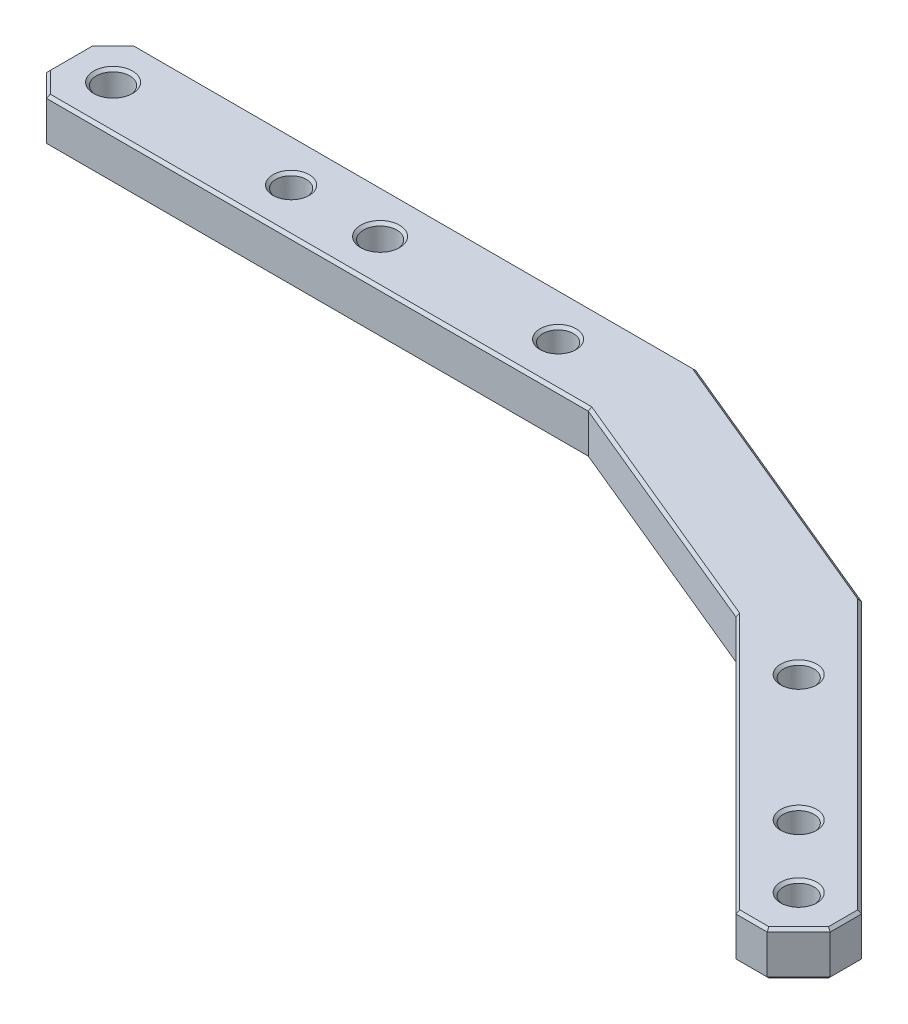
SolidWorks part; units mm, degrees
ref_plane "Front Plane" through (0, 0, 0) normal (0, 0, 1) x (1, 0, 0)
ref_plane "Top Plane" through (0, 0, 0) normal (0, 1, 0) x (1, 0, 0)
ref_plane "Right Plane" through (0, 0, 0) normal (1, 0, 0) x (0, 0, -1)
sketch "Sketch1" plane through (0, 0, 0) normal (0, 1, 0) x (1, 0, 0)
  line L0 (0, 0) -> (50.8, 0) construction
  line L1 (50.8, 0) -> (66.0533, -6.3181) construction
  line L2 (66.0533, -6.3181) -> (110.9545, -51.2194) construction
  line L3 (0, 0) -> (-38.1, 0) construction
  line L4 (-44.45, 6.35) -> (62.3654, 6.35)
  line L5 (62.3654, 6.35) -> (119.9348, -51.2194)
  line L6 (119.9348, -51.2194) -> (110.9545, -60.1996)
  line L7 (110.9545, -60.1996) -> (57.1049, -6.35)
  line L8 (57.1049, -6.35) -> (-44.45, -6.35)
  line L9 (-44.45, -6.35) -> (-44.45, 6.35)
  circle A2 centre (-38.1, 0) radius 2.3812
  circle A3 centre (0, 0) radius 2.3813
  circle A4 centre (110.9545, -51.2194) radius 2.1828
  circle A5 centre (101.9743, -42.2391) radius 2.1828
  circle A6 centre (-12.7, 0) radius 2.1828
  circle A7 centre (25.4, 0) radius 2.1828
  circle A8 centre (84.0138, -24.2786) radius 2.1828
  point P7 (0, 0)
  point P11 (0, 0)
  point P27 (0, 0)
  dimension "D16" = 4.3656
  dimension "D17" = 4.3656
  dimension "D18" = 4.7625
  dimension "D19" = 4.7625
  dimension "D22" = 4.3656
  dimension "D23" = 4.3656
  dimension "D25" = 4.3656
  dimension "D1" = 16.51
  dimension "D2" = 50.8
  dimension "D3" = 63.5
  dimension "D4" = 22.5
  dimension "D5" = 22.5
  dimension "D6" = 38.1
  dimension "D7" = 6.35
  dimension "D8" = 6.35
  dimension "D9" = 6.35
  dimension "D10" = 6.35
  dimension "D11" = 6.35
  dimension "D12" = 6.35
  dimension "D15" = 12.7
  dimension "D20" = 12.7
  dimension "D21" = 25.4
  dimension "D24" = 25.4
extrude "Boss-Extrude1" add sketch "Sketch1" along normal blind 6.35
fillet "Fillet1" radius 50.8 1 edges at (57.1049, 3.175, 6.35) profile chamfer
fillet "Fillet2" radius 57.15 1 edges at (62.3654, 3.175, -6.35) profile chamfer
chamfer "Chamfer1" distance 3.175 angle 45 4 edges at (-44.45, 3.175, -6.35) (-44.45, 3.175, 6.35) (110.9545, 3.175, 60.1996) (119.9348, 3.175, 51.2194)
chamfer "Chamfer2" distance 0.3969 angle 45 38 edges at (84.0138, 0, 26.4614) (-12.7, 0, 2.1828) (110.9545, 0, 53.4022) (0, 0, 2.3813) (-42.8625, 0, 4.7625) (-2.6061, 0, 6.35) (54.0234, 0, 13.7895) (90.3467, 0, 39.5918) (110.9545, 0, 57.9546) (115.4447, 0, 55.7095) (117.6897, 0, 51.2194) (98.397, 0, 29.6816) (58.8987, 0, 2.0194) (-1.291, 0, -6.35) (-42.8625, 0, -4.7625) (-44.45, 0, 0) (-38.1, 0, 2.3813) (101.9743, 0, 44.4219) (25.4, 0, 2.1828) (84.0138, 6.35, 26.4614) (25.4, 6.35, 2.1828) (-12.7, 6.35, 2.1828) (101.9743, 6.35, 44.4219) (110.9545, 6.35, 53.4022) (-38.1, 6.35, 2.3813) (0, 6.35, 2.3813) (58.8987, 6.35, 2.0194) (98.397, 6.35, 29.6816) (117.6897, 6.35, 51.2194) (115.4447, 6.35, 55.7095) (110.9545, 6.35, 57.9546) (90.3467, 6.35, 39.5918) (54.0234, 6.35, 13.7895) (-2.6061, 6.35, 6.35) (-42.8625, 6.35, 4.7625) (-44.45, 6.35, 0) (-42.8625, 6.35, -4.7625) (-1.291, 6.35, -6.35)
